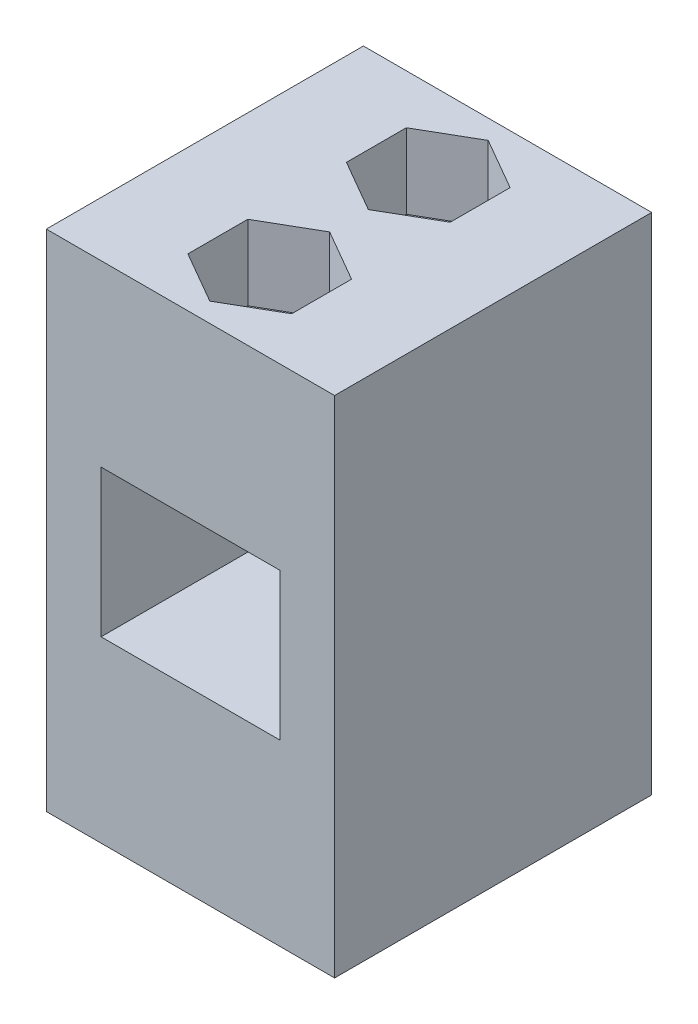
SolidWorks part; units mm, degrees
ref_plane "Front Plane" through (0, 0, 0) normal (0, 0, 1) x (1, 0, 0)
ref_plane "Top Plane" through (0, 0, 0) normal (0, 1, 0) x (1, 0, 0)
ref_plane "Right Plane" through (0, 0, 0) normal (1, 0, 0) x (0, 0, -1)
sketch "Sketch1" plane through (0, 0, 0) normal (1, 0, 0) x (0, 0, -1)
  line L1 (-11, 17.5) -> (11, 17.5)
  line L2 (-11, 17.5) -> (-11, -17.5)
  line L3 (-11, -17.5) -> (11, -17.5)
  line L4 (11, 17.5) -> (11, -17.5)
  line L5 (-11, 17.5) -> (11, -17.5) construction
  line L6 (-11, -17.5) -> (11, 17.5) construction
  point P0 (0, 0)
  dimension "D1" = 35
  dimension "D2" = 22
extrude "Boss-Extrude1" add sketch "Sketch1" along normal blind 10 and the other way blind 10
sketch "Sketch2" plane through (0, 0, 11) normal (0, 0, 1) x (1, 0, 0)
  line L1 (-6.2, 5.1) -> (6.2, 5.1)
  line L2 (-6.2, 5.1) -> (-6.2, -5.1)
  line L3 (-6.2, -5.1) -> (6.2, -5.1)
  line L4 (6.2, 5.1) -> (6.2, -5.1)
  line L5 (-6.2, 5.1) -> (6.2, -5.1) construction
  line L6 (-6.2, -5.1) -> (6.2, 5.1) construction
  point P0 (0, 0)
  dimension "D1" = 12.4
  dimension "D2" = 10.2
extrude "Cut-Extrude1" cut sketch "Sketch2" against normal through all both and the other way through all
sketch "Sketch3" plane through (0, 17.5, 0) normal (0, 1, 0) x (1, 0, 0)
  line L0 (0, -12.1) -> (0, 12.1) construction
  line L1 (3.6, 7.5785) -> (0, 9.6569)
  line L2 (0, 9.6569) -> (-3.6, 7.5785)
  line L3 (-3.6, 7.5785) -> (-3.6, 3.4215)
  line L4 (-3.6, 3.4215) -> (0, 1.3431)
  line L5 (0, 1.3431) -> (3.6, 3.4215)
  line L6 (3.6, 3.4215) -> (3.6, 7.5785)
  line L7 (0, 11) -> (0, 0) construction
  line L8 (-10, 11) -> (10, 11) construction
  line L9 (-11, 0) -> (11, 0) construction
  circle A0 centre (0, 5.5) radius 3.6 construction
  point P10 (0, 0)
  point P16 (0, 5.5)
  dimension "D1" = 7.2
extrude "Cut-Extrude2" cut sketch "Sketch3" against normal blind 5.2
mirror "Mirror1" about plane through (0, 0, 0) normal (0, 1, 0) of "Cut-Extrude2" second plane through (0, 0, 0) second plane normal (0, 0, 1)
